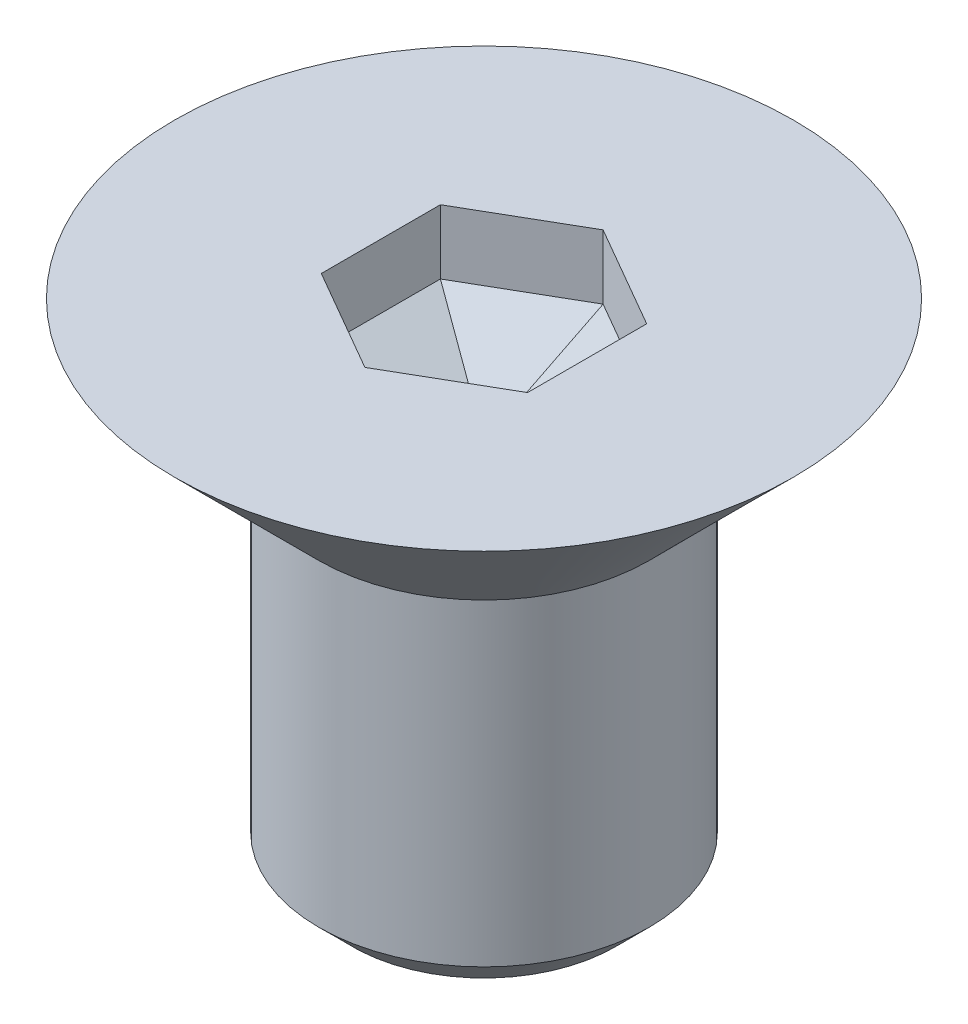
SolidWorks part; units mm, degrees
ref_plane "前视基准面" through (0, 0, 0) normal (0, 0, 1) x (1, 0, 0)
ref_plane "上视基准面" through (0, 0, 0) normal (0, 1, 0) x (1, 0, 0)
ref_plane "右视基准面" through (0, 0, 0) normal (1, 0, 0) x (0, 0, -1)
sketch "草图2" plane through (0, 0, 0) normal (0, 0, 1) x (1, 0, 0)
  line L0 (0, -2.48) -> (0, 0)
  line L1 (0, 0) -> (3.75, 0)
  line L2 (3.75, 0) -> (1.27, -2.48)
  line L3 (1.27, -2.48) -> (0, -2.48)
  dimension "D1" = 45
  dimension "k" = 2.48
  dimension "dk/2" = 3.75
revolve "旋转1" add sketch "草图2" angle 360 about L0
sketch "草图4" plane through (0, 0, 0) normal (0, -1, 0) x (1, 0, 0)
  circle A0 centre (0, 0) radius 2
  dimension "d" = 4
extrude "凸台-拉伸2" add sketch "草图4" along normal blind 6
cosmetic thread "装饰螺纹线1" parameters "D2"=1.221
sketch "草图3" plane through (0, 0, 0) normal (0, 1, 0) x (1, 0, 0)
  line L1 (1.25, 0.7217) -> (0, 1.4434)
  line L2 (0, 1.4434) -> (-1.25, 0.7217)
  line L3 (-1.25, 0.7217) -> (-1.25, -0.7217)
  line L4 (-1.25, -0.7217) -> (0, -1.4434)
  line L5 (0, -1.4434) -> (1.25, -0.7217)
  line L6 (1.25, -0.7217) -> (1.25, 0.7217)
  circle A0 centre (0, 0) radius 1.25 construction
  dimension "S" = 2.5
extrude "切除-拉伸1" cut sketch "草图3" against normal blind 1.5
chamfer "倒角3" distance 0.7205 angle 60 6 edges at (-0.625, -1.5, 1.0825) (-1.25, -1.5, 0) (-0.625, -1.5, -1.0825) (0.625, -1.5, -1.0825) (1.25, -1.5, 0) (0.625, -1.5, 1.0825) first distance on face at (-0.625, -0.75, 1.0825) first distance on face at (-1.25, -0.75, 0) first distance on face at (-0.625, -0.75, -1.0825) first distance on face at (0.625, -0.75, -1.0825) first distance on face at (1.25, -0.75, 0) first distance on face at (0.625, -0.75, 1.0825)
chamfer "倒角4" distance 0.4 angle 45 1 edges at (0, -6, -2)
ref_axis "基准轴1" through (0, -5.6, 0) along (0, 1, 0)
ref_plane "基准面1" through (0, 0, 0) normal (0, -1, 0) x (-1, 0, 0)
equation "\"D1@倒角3\"= \"S@草图3\" / 3.47"
equation "\"D1@倒角4\"= \"d@草图4\" / 10"
